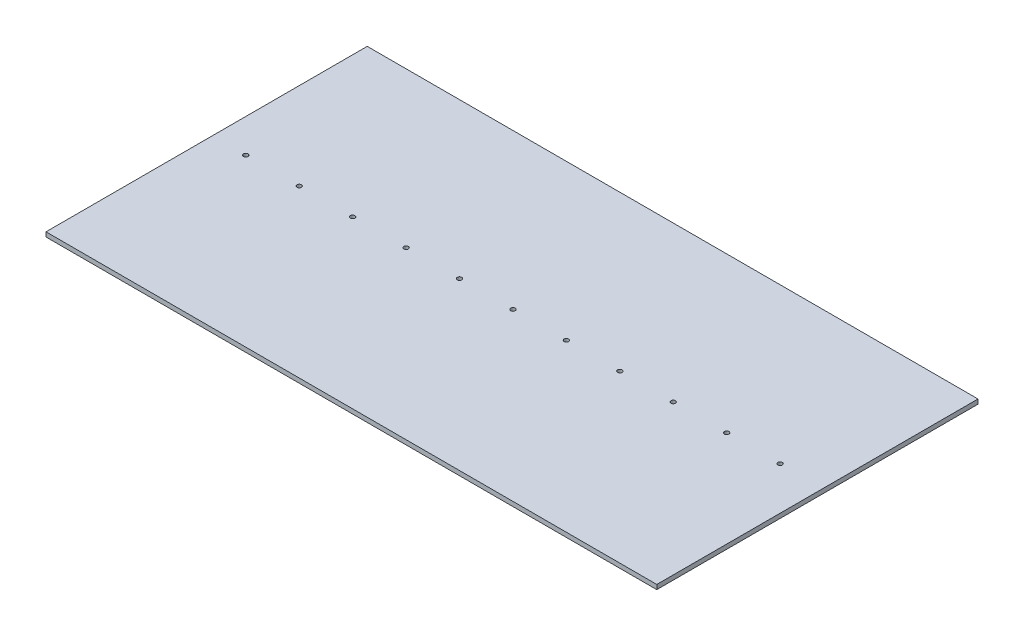
SolidWorks part; units mm, degrees
ref_plane "Front Plane" through (0, 0, 0) normal (0, 0, 1) x (1, 0, 0)
ref_plane "Top Plane" through (0, 0, 0) normal (0, 1, 0) x (1, 0, 0)
ref_plane "Right Plane" through (0, 0, 0) normal (1, 0, 0) x (0, 0, -1)
sketch "Sketch1" plane through (0, 0, 0) normal (0, 1, 0) x (1, 0, 0)
  line L1 (0, 0) -> (857.25, 0)
  line L2 (0, 0) -> (0, 450.85)
  line L3 (0, 450.85) -> (857.25, 450.85)
  line L4 (857.25, 0) -> (857.25, 450.85)
  dimension "D1" = 450.85
  dimension "D2" = 857.25
extrude "Boss-Extrude1" add sketch "Sketch1" along normal blind 6.35
sketch "Sketch2" plane through (0, 6.35, 0) normal (0, 1, 0) x (1, 0, 0)
  line L3 (47.052, 233.3421) -> (122.052, 233.3421) construction
  line L4 (857.25, 0) -> (857.25, 450.85) construction
  circle A0 centre (47.052, 233.3421) radius 3.175
  circle A1 centre (647.052, 233.3421) radius 3.175
  circle A2 centre (122.052, 233.3421) radius 3.175
  circle A3 centre (197.052, 233.3421) radius 3.175
  circle A4 centre (272.052, 233.3421) radius 3.175
  circle A5 centre (347.052, 233.3421) radius 3.175
  circle A6 centre (422.052, 233.3421) radius 3.175
  circle A7 centre (497.052, 233.3421) radius 3.175
  circle A8 centre (572.052, 233.3421) radius 3.175
  circle A9 centre (722.052, 233.3421) radius 3.175
  circle A10 centre (797.052, 233.3421) radius 3.175
  dimension "D1" = 6.35
  dimension "D4" = 75
  dimension "D11" = 60.198
  dimension "D2" = 75
  dimension "D3" = 75
  dimension "D5" = 75
  dimension "D6" = 75
  dimension "D7" = 75
  dimension "D8" = 75
  dimension "D9" = 75
  dimension "D10" = 75
  dimension "D12" = 75
extrude "Cut-Extrude1" cut sketch "Sketch2" against normal through all both and the other way through all
